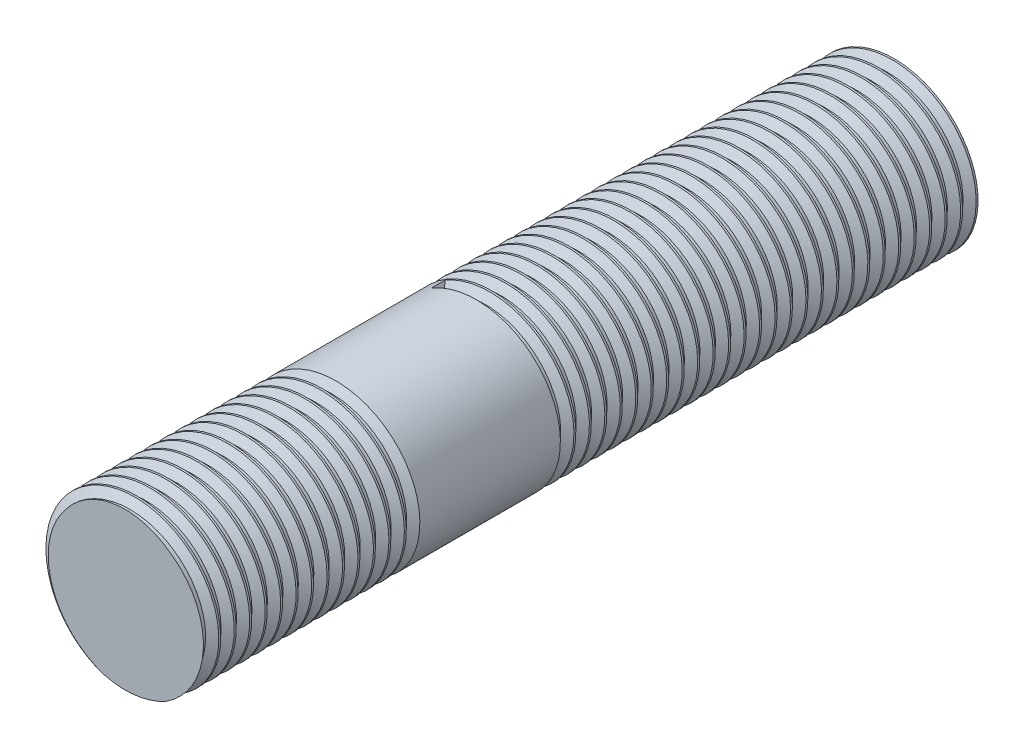
SolidWorks part; units mm, degrees
material "Commercial Bronze, UNS C22000 (90-10 Bronze)"
ref_plane "Front Plane" through (0, 0, 0) normal (0, 0, 1) x (1, 0, 0)
ref_plane "Top Plane" through (0, 0, 0) normal (0, 1, 0) x (1, 0, 0)
ref_plane "Right Plane" through (0, 0, 0) normal (1, 0, 0) x (0, 0, -1)
sketch "Sketch1" plane through (0, 0, 0) normal (0, 0, 1) x (1, 0, 0)
  circle A0 centre (0, 0) radius 8
  dimension "D1" = 16
extrude "Boss-Extrude1" add sketch "Sketch1" along normal blind 75
thread "Thread1" pitch 1.5 method cut profile "Thread Profile1" start angle 0, offset 10, length 30, pitch 1.5, diameter 16
ref_plane "Plane1" through (-8, 0, 85) normal (0, -1, 0) x (-1, 0, 0)
sketch "Thread Profile1" plane through (-8, 0, 85) normal (0, -1, 0) x (-1, 0, 0)
  line L0 (0, 0) -> (0, 1.5) construction
  line L11 (0, 0) -> (0, 1.3125)
  line L12 (0, 1.3125) -> (-0.8119, 0.8437)
  line L13 (-0.8119, 0.8437) -> (-0.8119, 0.4687)
  line L15 (-0.8119, 0.4687) -> (0, 0)
  line L17 (-0.8119, 0.6562) -> (0, 0.6562) construction
  point P2 (0, 0)
  dimension "Pitch" = 1.5
  dimension "Profile_Angle" = 60
  dimension "Profile_Land" = 0.375
  dimension "Profile_Height" = 0.8119
thread "Thread2" pitch 1.5 method cut profile "Thread Profile2" start angle 0, offset 10, length 50, pitch 1.5, diameter 16
ref_plane "Plane2" through (8, 0, -10) normal (0, -1, 0) x (1, 0, 0)
sketch "Thread Profile2" plane through (8, 0, -10) normal (0, -1, 0) x (1, 0, 0)
  line L0 (0, 0) -> (0, 1.5) construction
  line L11 (0, 0) -> (0, 1.3125)
  line L12 (0, 1.3125) -> (-0.8119, 0.8437)
  line L13 (-0.8119, 0.8437) -> (-0.8119, 0.4687)
  line L15 (-0.8119, 0.4687) -> (0, 0)
  line L17 (-0.8119, 0.6562) -> (0, 0.6562) construction
  point P2 (0, 0)
  dimension "Pitch" = 1.5
  dimension "Profile_Angle" = 60
  dimension "Profile_Land" = 0.375
  dimension "Profile_Height" = 0.8119
